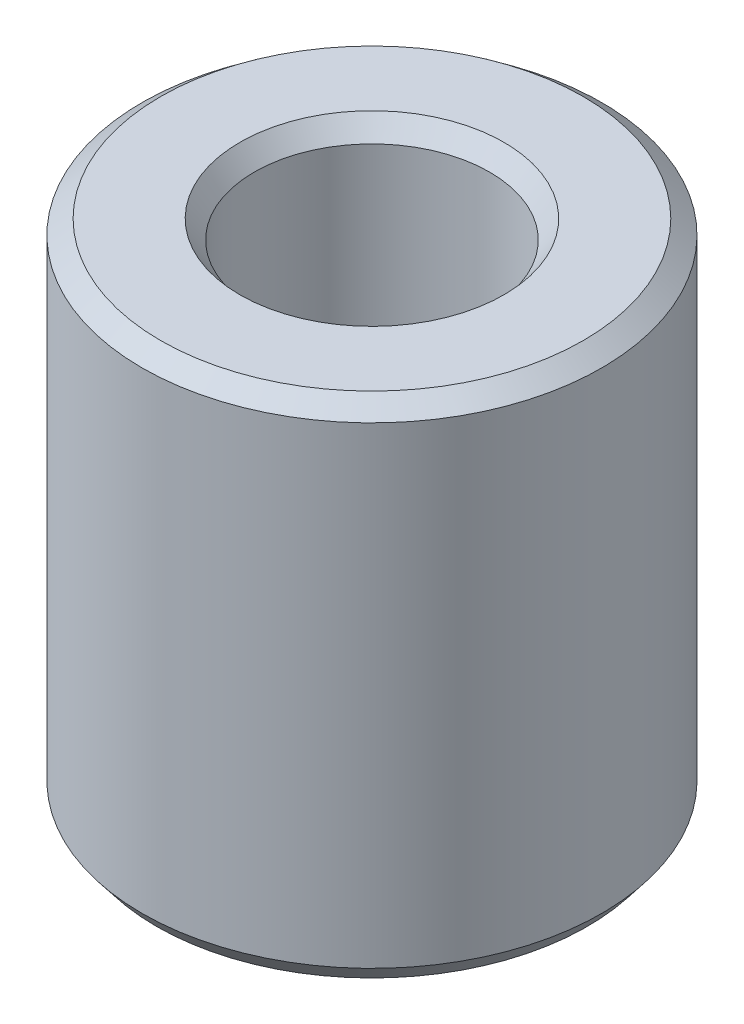
SolidWorks part; units mm, degrees
ref_plane "Front Plane" through (0, 0, 0) normal (0, 0, 1) x (1, 0, 0)
ref_plane "Top Plane" through (0, 0, 0) normal (0, 1, 0) x (1, 0, 0)
ref_plane "Right Plane" through (0, 0, 0) normal (1, 0, 0) x (0, 0, -1)
sketch "Sketch1" plane through (0, 0, 0) normal (0, 1, 0) x (1, 0, 0)
  circle A0 centre (0, 0) radius 5
  dimension "SLEEVE_OD" = 10
extrude "Boss-Extrude1" add sketch "Sketch1" along normal blind 10.9929
sketch "Sketch2" plane through (0, 0, 0) normal (0, 1, 0) x (1, 0, 0)
  circle A0 centre (0, 0) radius 2.5593
  dimension "BORE_D" = 5.1185
extrude "Cut-Extrude1" cut sketch "Sketch2" along normal through all
chamfer "Chamfer1" distance 0.3138 angle 52.093 4 edges at (0, 10.9929, 2.5593) (0, 0, 2.5593) (0, 0, 5) (0, 10.9929, 5) first distance on face at (0, 10.9929, 2.5593) first distance on face at (0, 0, 2.5593) first distance on face at (0, 10.9929, 5)
